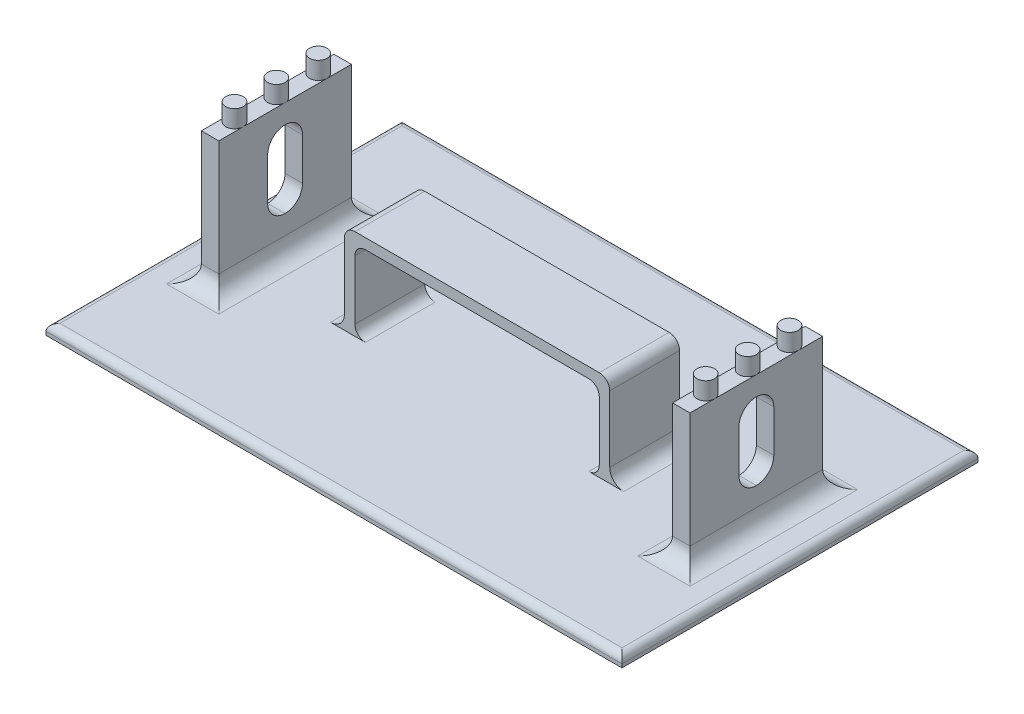
SolidWorks part; units mm, degrees
material "PVAL"
ref_plane "Front Plane" through (0, 0, 0) normal (0, 0, 1) x (1, 0, 0)
ref_plane "Top Plane" through (0, 0, 0) normal (0, 1, 0) x (1, 0, 0)
ref_plane "Right Plane" through (0, 0, 0) normal (1, 0, 0) x (0, 0, -1)
other "Center of Mass"
sketch "Sketch1" plane through (0, 0, 0) normal (0, 1, 0) x (1, 0, 0)
  line L1 (0, 0) -> (165, 0)
  line L2 (0, 0) -> (0, 90)
  line L3 (0, 90) -> (165, 90)
  line L4 (165, 0) -> (165, 90)
  dimension "D1" = 90
  dimension "D2" = 165
extrude "Boss-Extrude1" add sketch "Sketch1" along normal blind 3
sketch "Sketch2" plane through (0, 3, 0) normal (0, 1, 0) x (1, 0, 0)
  line L0 (82.5, 0) -> (82.5, 90) construction
  line L1 (0, 0) -> (165, 0) construction
  line L2 (165, 90) -> (0, 90) construction
  line L3 (0, 45) -> (165, 45) construction
  line L4 (0, 90) -> (0, 0) construction
  line L5 (165, 0) -> (165, 90) construction
  line L6 (12.5, 26) -> (17.5, 26)
  line L8 (12.5, 26) -> (12.5, 64)
  line L10 (17.5, 26) -> (17.5, 64)
  line L12 (147.5, 26) -> (147.5, 64)
  line L14 (152.5, 26) -> (152.5, 64)
  line L16 (12.5, 64) -> (17.5, 64)
  line L18 (147.5, 64) -> (152.5, 64)
  line L20 (147.5, 26) -> (152.5, 26)
  point P22 (150, 64)
  dimension "D1" = 70
  dimension "D2" = 70
  dimension "D3" = 65
  dimension "D4" = 65
  dimension "D5" = 19
  dimension "D6" = 19
  dimension "D7" = 19
  dimension "D8" = 19
extrude "Boss-Extrude3" add sketch "Sketch2" along normal blind 38
fillet "Fillet1" radius 5 8 edges at (15, 3, -64) (12.5, 3, -45) (17.5, 3, -45) (15, 3, -26) (150, 3, -26) (152.5, 3, -45) (150, 3, -64) (147.5, 3, -45)
sketch "Sketch3" plane through (0, 41, 0) normal (0, 1, 0) x (1, 0, 0)
  line L0 (15, 64) -> (15, 26) construction
  line L1 (17.5, 64) -> (12.5, 64) construction
  line L2 (12.5, 26) -> (17.5, 26) construction
  line L4 (152.5, 64) -> (147.5, 64) construction
  line L5 (150, 64) -> (150, 26) construction
  line L6 (147.5, 26) -> (152.5, 26) construction
  line L8 (152.5, 26) -> (152.5, 64) construction
  line L9 (152.5, 45) -> (12.5, 45) construction
  line L10 (12.5, 64) -> (12.5, 26) construction
  circle A0 centre (15, 57) radius 2.5
  circle A1 centre (15, 33) radius 2.5
  circle A2 centre (150, 57) radius 2.5
  circle A3 centre (150, 33) radius 2.5
  dimension "D1" = 12
  dimension "D2" = 12
  dimension "D3" = 12
  dimension "D4" = 12
extrude "Boss-Extrude4" add sketch "Sketch3" along normal blind 5
sketch "Sketch4" plane through (0, 3, 0) normal (0, 1, 0) x (1, 0, 0)
  line L0 (165, 45) -> (0, 45) construction
  line L1 (165, 0) -> (165, 90) construction
  line L2 (0, 90) -> (0, 0) construction
  line L4 (0, 0) -> (165, 0) construction
  line L5 (82.5, 0) -> (82.5, 90) construction
  line L6 (165, 90) -> (0, 90) construction
  line L7 (120.5, 55) -> (117.5, 55)
  line L8 (120.5, 55) -> (120.5, 35)
  line L9 (120.5, 35) -> (117.5, 35)
  line L10 (117.5, 55) -> (117.5, 35)
  line L11 (120.5, 55) -> (117.5, 35) construction
  line L12 (120.5, 35) -> (117.5, 55) construction
  line L13 (47.5, 55) -> (44.5, 55)
  line L14 (47.5, 55) -> (47.5, 35)
  line L15 (47.5, 35) -> (44.5, 35)
  line L16 (44.5, 55) -> (44.5, 35)
  line L17 (47.5, 55) -> (44.5, 35) construction
  line L18 (47.5, 35) -> (44.5, 55) construction
  point P6 (119, 45)
  point P17 (46, 45)
  point P22 (46, 35)
  dimension "D1" = 35
  dimension "D2" = 35
  dimension "D3" = 20
  dimension "D4" = 20
  dimension "D5" = 3
  dimension "D6" = 3
extrude "Boss-Extrude5" add sketch "Sketch4" along normal blind 23
sketch "Sketch5" plane through (0, 26, 0) normal (0, 1, 0) x (1, 0, 0)
  line L0 (120.5, 35) -> (44.5, 35)
  line L1 (44.5, 35) -> (44.5, 55)
  line L2 (44.5, 55) -> (120.5, 55)
  line L3 (120.5, 55) -> (120.5, 35)
extrude "Boss-Extrude6" add sketch "Sketch5" along normal blind 3
fillet "Fillet3" radius 3 4 edges at (47.5, 26, -45) (117.5, 26, -45) (47.5, 3, -45) (117.5, 3, -45)
fillet "Fillet4" radius 3 2 edges at (120.5, 29, -45) (44.5, 29, -45)
sketch "Sketch8" plane through (12.5, 0, 0) normal (-1, 0, 0) x (0, 0, 1)
  line L0 (-26, 24.5) -> (-64, 24.5) construction
  line L2 (-26, 41) -> (-26, 8) construction
  line L3 (-64, 41) -> (-64, 8) construction
  line L4 (-45, 8) -> (-45, 41) construction
  line L5 (-64, 8) -> (-26, 8) construction
  line L6 (-57, 41) -> (-33, 41) construction
  line L8 (-40, 35.5) -> (-50, 35.5)
  line L9 (-40, 35.5) -> (-40, 13.5)
  line L10 (-40, 13.5) -> (-50, 13.5)
  line L11 (-50, 35.5) -> (-50, 13.5)
  line L12 (-40, 35.5) -> (-50, 13.5) construction
  line L13 (-40, 13.5) -> (-50, 35.5) construction
  point P12 (-45, 24.5)
  dimension "D1" = 10
  dimension "D2" = 22
extrude "Cut-Extrude1" cut sketch "Sketch8" against normal blind 10
fillet "Fillet10" radius 5 4 edges at (15, 13.5, -50) (15, 35.5, -50) (15, 13.5, -40) (15, 35.5, -40)
sketch "Sketch9" plane through (152.5, 0, 0) normal (1, 0, 0) x (0, 0, -1)
  line L0 (64, 24.5) -> (26, 24.5) construction
  line L1 (64, 41) -> (64, 8) construction
  line L2 (26, 41) -> (26, 8) construction
  line L3 (45, 8) -> (45, 41) construction
  line L4 (26, 8) -> (64, 8) construction
  line L5 (33, 41) -> (57, 41) construction
  line L7 (50, 35.5) -> (40, 35.5)
  line L8 (50, 35.5) -> (50, 13.5)
  line L9 (50, 13.5) -> (40, 13.5)
  line L10 (40, 35.5) -> (40, 13.5)
  line L11 (50, 35.5) -> (40, 13.5) construction
  line L12 (50, 13.5) -> (40, 35.5) construction
  point P12 (45, 24.5)
  dimension "D1" = 10
  dimension "D2" = 22
extrude "Cut-Extrude2" cut sketch "Sketch9" against normal blind 10
fillet "Fillet11" radius 5 4 edges at (150, 35.5, -40) (150, 13.5, -40) (150, 13.5, -50) (150, 35.5, -50)
sketch "Sketch10" plane through (0, 0, 0) normal (0, -1, 0) x (1, 0, 0)
  line L1 (165, -90) -> (0, -90)
  line L2 (165, -90) -> (165, -96)
  line L3 (165, -96) -> (0, -96)
  line L4 (0, -90) -> (0, -96)
  line L5 (165, 0) -> (0, 0)
  line L6 (165, 0) -> (165, 6)
  line L7 (165, 6) -> (0, 6)
  line L8 (0, 0) -> (0, 6)
  dimension "D1" = 6
  dimension "D2" = 6
  dimension "D3" = 165
  dimension "D4" = 165
extrude "Boss-Extrude9" add sketch "Sketch10" against normal blind 3
fillet "Fillet13" radius 4 2 edges at (44.5, 3, -45) (120.5, 3, -45)
sketch "Sketch11" plane through (0, 41, 0) normal (0, 1, 0) x (1, 0, 0)
  line L0 (150, 33) -> (150, 57) construction
  line L1 (15, 33) -> (15, 57) construction
  circle A0 centre (150, 45) radius 2.5
  circle A1 centre (15, 45) radius 2.5
  dimension "D1" = 5
  dimension "D2" = 5
extrude "Boss-Extrude10" add sketch "Sketch11" along normal blind 5
fillet "Fillet14" radius 2 4 edges at (82.5, 3, -96) (165, 3, -45) (0, 3, -45) (82.5, 3, 6)
